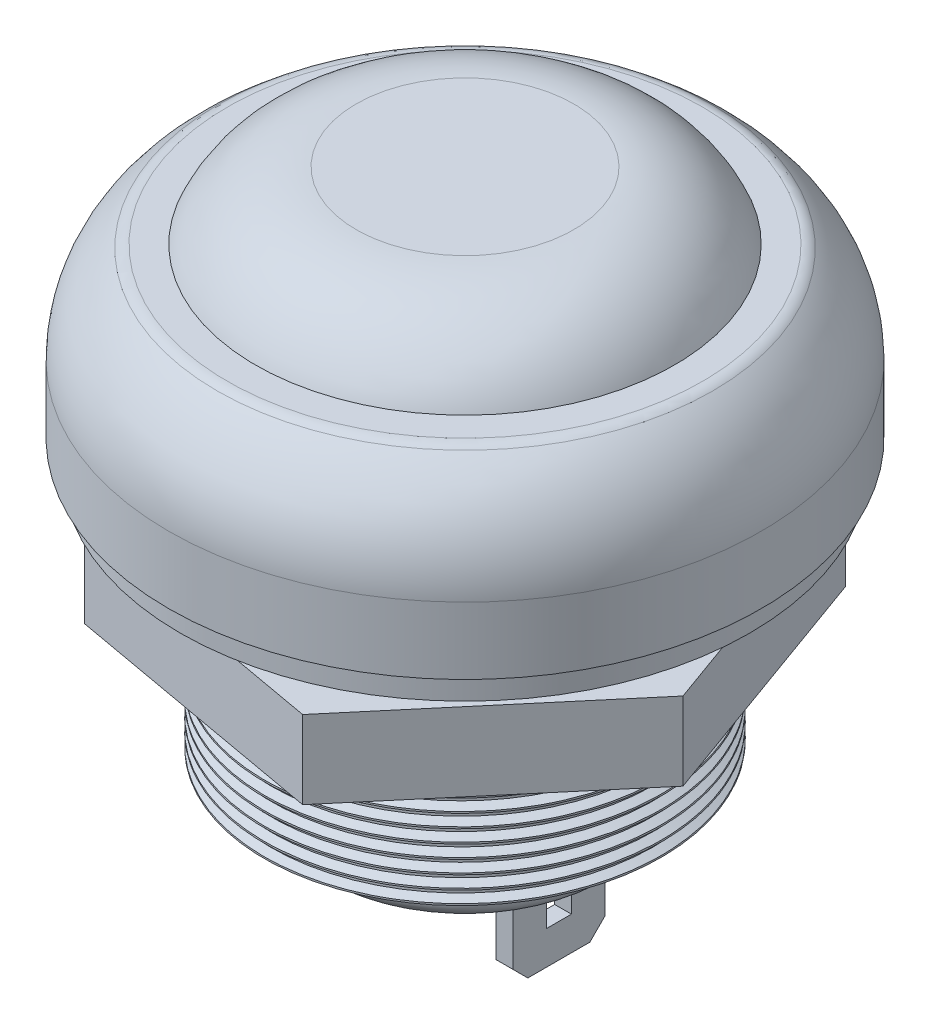
SolidWorks part; units mm, degrees
ref_plane "Front Plane" through (0, 0, 0) normal (0, 0, 1) x (1, 0, 0)
ref_plane "Top Plane" through (0, 0, 0) normal (0, 1, 0) x (1, 0, 0)
ref_plane "Right Plane" through (0, 0, 0) normal (1, 0, 0) x (0, 0, -1)
sketch "Sketch1" plane through (0, 0, 0) normal (0, 0, 1) x (1, 0, 0)
  line L0 (0, 6.5) -> (0, -6.5)
  line L1 (0, 6.5) -> (0, -6.5) construction
  line L2 (0, 6.5) -> (8.84, 6.5)
  line L3 (8.84, 6.5) -> (8.84, 1.5)
  line L4 (8.84, 1.5) -> (6.74, 1.5)
  line L5 (6.74, 1.5) -> (6.74, -0.3)
  line L6 (6.74, -0.3) -> (5.915, -0.3)
  line L7 (5.915, -0.3) -> (5.915, -6.5)
  line L8 (5.915, -6.5) -> (0, -6.5)
  dimension "D1" = 5.915
  dimension "D2" = 6.74
  dimension "D3" = 13
  dimension "D4" = 8.84
  dimension "D5" = 6.2
  dimension "D6" = 8
revolve "Revolve1" add sketch "Sketch1" angle 360 about L1
sketch "Sketch2" plane through (0, -6.5, 0) normal (0, -1, 0) x (1, 0, 0)
  circle A0 centre (0, 0) radius 4.295
  dimension "D1" = 8.59
extrude "Boss-Extrude1" add sketch "Sketch2" along normal blind 1.5 separate body
sketch "Sketch3" plane through (0, -8, 0) normal (0, -1, 0) x (1, 0, 0)
  line L0 (0, 4.295) -> (0, -4.295) construction
  line L1 (-2.55, 4.295) -> (-2.55, -4.295) construction
  line L2 (2.55, 4.295) -> (2.55, -4.295) construction
  line L3 (-4.295, 0) -> (4.295, 0) construction
  line L4 (-4.295, -1.375) -> (4.295, -1.375) construction
  line L5 (-4.295, 1.375) -> (4.295, 1.375) construction
  line L7 (2.3, -1.375) -> (2.8, -1.375)
  line L8 (2.3, -1.375) -> (2.3, 1.375)
  line L9 (2.3, 1.375) -> (2.8, 1.375)
  line L10 (2.8, -1.375) -> (2.8, 1.375)
  line L11 (2.3, -1.375) -> (2.8, 1.375) construction
  line L12 (2.3, 1.375) -> (2.8, -1.375) construction
  line L13 (-2.8, -1.375) -> (-2.3, -1.375)
  line L14 (-2.8, -1.375) -> (-2.8, 1.375)
  line L15 (-2.8, 1.375) -> (-2.3, 1.375)
  line L16 (-2.3, -1.375) -> (-2.3, 1.375)
  line L17 (-2.8, -1.375) -> (-2.3, 1.375) construction
  line L18 (-2.8, 1.375) -> (-2.3, -1.375) construction
  circle A0 centre (0, 0) radius 4.295 construction
  point P15 (2.55, 0)
  point P20 (-2.55, 0)
  dimension "D5" = 0.5
  dimension "D6" = 0.5
  dimension "D1" = 2.55
  dimension "D2" = 2.55
  dimension "D3" = 1.375
  dimension "D4" = 1.375
extrude "Boss-Extrude2" add sketch "Sketch3" along normal blind 2.6 separate body
sketch "Sketch5" plane through (0, 6.5, 0) normal (0, 1, 0) x (1, 0, 0)
  circle A0 centre (0, 0) radius 6.25
  dimension "D1" = 12.5
extrude "Boss-Extrude3" add sketch "Sketch5" along normal blind 2 separate body
sketch "Sketch6" plane through (0, 8.5, 0) normal (0, 1, 0) x (1, 0, 0)
  circle A0 centre (0, 0) radius 3.25
  dimension "D1" = 6.5
sketch "Sketch8" plane through (0, 0, 0) normal (0, 0, 1) x (1, 0, 0)
  line L1 (0, 8.5) -> (0, -8.0216) construction
  line L2 (3.25, 8.5) -> (-3.25, 8.5) construction
  line L7 (3.25, 8.5) -> (3.25, 9.8195)
  line L8 (3.25, 9.8195) -> (7.0951, 9.8195)
  line L9 (7.0951, 9.8195) -> (7.0951, 6.5)
  line L10 (7.0951, 6.5) -> (6.25, 6.5)
  arc A0 (3.25, 8.5) -> (6.25, 6.5) centre (3.25, 5.25) cw
  dimension "D7" = 3.25
  dimension "D1" = 1.3195
  dimension "D2" = 3.3195
  dimension "D3" = 3.8451
  dimension "D4" = 3.25
  dimension "D5" = 6.25
  dimension "D6" = 0.8451
revolve "Cut-Revolve1" cut sketch "Sketch8" angle 360 about L1
sketch "Sketch9" plane through (0, 0, 0) normal (0, 0, 1) x (1, 0, 0)
  line L0 (0, 8.5) -> (0, -8) construction
  line L1 (3.25, 8.5) -> (-3.25, 8.5) construction
  line L2 (-4.295, -8) -> (4.295, -8) construction
  line L3 (8.84, 3.5) -> (9.5988, 3.5)
  line L4 (9.5988, 3.5) -> (9.5988, 6.8651)
  line L5 (9.5988, 6.8651) -> (7.25, 6.8651)
  line L7 (7.25, 6.5) -> (7.25, 6.8651)
  arc A0 (7.25, 6.5) -> (8.84, 3.5) centre (5.2148, 3.5) cw
  point P6 (9.5988, 5.1826)
  dimension "D5" = 3.6252
  dimension "D1" = 7.25
  dimension "D2" = 9.5988
  dimension "D3" = 3.5
  dimension "D4" = 6.8651
  dimension "D6" = 3.3953
revolve "Cut-Revolve2" cut sketch "Sketch9" angle 360 about L0
thread "Thread1" pitch 0.3969 method cut profile "Thread Profile1" start angle 0, offset 1, length 0, pitch 0.3969, diameter 11.83
ref_plane "Plane1" through (5.915, -7.5, 0) normal (0, 0, 1) x (1, 0, 0)
sketch "Thread Profile1" plane through (5.915, -7.5, 0) normal (0, 0, 1) x (1, 0, 0)
  line L0 (0, 0) -> (0, 0.3969) construction
  line L11 (0, 0) -> (0, 0.3473)
  line L12 (0, 0.3473) -> (-0.2148, 0.2232)
  line L13 (-0.2148, 0.2232) -> (-0.2148, 0.124)
  line L15 (-0.2148, 0.124) -> (0, 0)
  line L17 (-0.2148, 0.1736) -> (0, 0.1736) construction
  point P2 (0, 0)
  dimension "Pitch" = 0.3969
  dimension "Profile_Angle" = 60
  dimension "Profile_Land" = 0.0992
  dimension "Profile_Height" = 0.2148
sketch "Sketch14" plane through (-2.8, 0, 0) normal (-1, 0, 0) x (0, 0, 1)
  line L4 (1.375, -8) -> (-1.375, -8) construction
  line L5 (0.375, -8) -> (-0.375, -8)
  line L8 (0.375, -9) -> (-0.375, -9)
  line L9 (-0.375, -9) -> (-0.375, -9.6)
  line L10 (-0.375, -9.6) -> (0.375, -9.6)
  line L11 (0.375, -9.6) -> (0.375, -9)
  line L12 (0.375, -9) -> (-0.375, -9) construction
  line L13 (-0.375, -8) -> (-0.375, -9.6)
  line L14 (-0.375, -9.6) -> (0.375, -9.6)
  line L15 (0.375, -9.6) -> (0.375, -8)
  dimension "D1" = 1
extrude "Cut-Extrude1" cut sketch "Sketch14" against normal up to surface (5.6 mm away) up to face at (2.8, -9.3, 0)
chamfer "Chamfer1" distance 0.45 angle 45 2 edges at (-2.55, -10.6, 1.375) (-2.55, -10.6, -1.375)
chamfer "Chamfer2" distance 0.45 angle 45 2 edges at (2.55, -10.6, 1.375) (2.55, -10.6, -1.375)
fillet "Fillet1" radius 0.5 1 edges at (0, 6.5, 7.25)
fillet "Fillet2" radius 0.5 1 edges at (0, -8, -4.295)
sketch "Sketch15" plane through (0, 1.5, 0) normal (0, -1, 0) x (1, 0, 0)
  circle A0 centre (0, 0) radius 8.5
  circle A1 centre (0, 0) radius 6.8
  dimension "D1" = 17
  dimension "D2" = 1.7
extrude "Boss-Extrude4" add sketch "Sketch15" along normal blind 0.8 separate body
ref_plane "Plane2" through (0, -0.5, 0) normal (0, -1, 0) x (-1, 0, 0)
sketch "Sketch16" plane through (0, -0.5, 0) normal (0, -1, 0) x (1, 0, 0)
  line L1 (5.1957, -6.1541) -> (7.9274, 1.4225)
  line L2 (7.9274, 1.4225) -> (2.7318, 7.5766)
  line L3 (2.7318, 7.5766) -> (-5.1957, 6.1541)
  line L4 (-5.1957, 6.1541) -> (-7.9274, -1.4225)
  line L5 (-7.9274, -1.4225) -> (-2.7318, -7.5766)
  line L6 (-2.7318, -7.5766) -> (5.1957, -6.1541)
  circle A0 centre (0, 0) radius 6.975 construction
  circle A1 centre (0, 0) radius 5.5
  dimension "D1" = 13.95
  dimension "D2" = 11
  dimension "D3" = 7.9274
extrude "Boss-Extrude5" add sketch "Sketch16" along normal blind 2.33 separate body
scale "Scale1" bodies to scale 109 102 111 110 105 113 112 scale about origin uniform scaling yes scale factor 2
